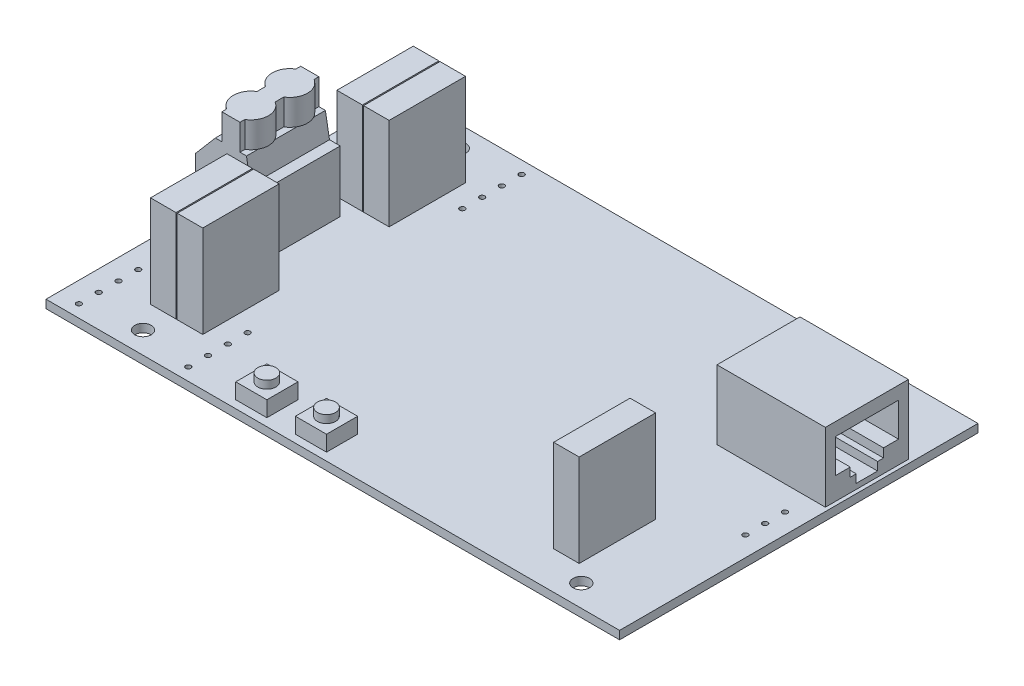
SolidWorks part; units mm, degrees
ref_plane "Front Plane" through (0, 0, 0) normal (0, 0, 1) x (1, 0, 0)
ref_plane "Top Plane" through (0, 0, 0) normal (0, 1, 0) x (1, 0, 0)
ref_plane "Right Plane" through (0, 0, 0) normal (1, 0, 0) x (0, 0, -1)
sketch "Sketch1" plane through (0, 0, 0) normal (0, 1, 0) x (1, 0, 0)
  line L0 (1.4606, 0) -> (0, 0) construction
  line L1 (-55.2894, -34.55) -> (55.2895, -34.55)
  line L2 (-55.2894, -34.55) -> (-55.2894, 34.55)
  line L3 (-55.2894, 34.55) -> (55.2895, 34.55)
  line L4 (55.2895, -34.55) -> (55.2895, 34.55)
  line L5 (-55.2894, -34.55) -> (55.2895, 34.55) construction
  line L6 (-55.2894, 34.55) -> (55.2895, -34.55) construction
  line L7 (-40.7894, -30.35) -> (43.7106, -30.35) construction
  line L8 (-40.7894, -30.35) -> (-40.7894, 30.35) construction
  line L9 (-40.7894, 30.35) -> (43.7106, 30.35) construction
  line L10 (43.7106, -30.35) -> (43.7106, 30.35) construction
  line L11 (-40.7894, -30.35) -> (43.7106, 30.35) construction
  line L12 (-40.7894, 30.35) -> (43.7106, -30.35) construction
  circle A0 centre (-40.7894, -30.35) radius 1.5875
  circle A1 centre (-40.7894, 30.35) radius 1.5875
  circle A2 centre (43.7106, 30.35) radius 1.5875
  circle A3 centre (43.7106, -30.35) radius 1.5875
  point P0 (0, 0)
  point P14 (0, 0)
  dimension "D3" = 3.175
  dimension "D6" = 4.2
  dimension "D7" = 14.5
  dimension "D1" = 69.1
  dimension "D2" = 110.5789
  dimension "D4" = 84.5
  dimension "D5" = 60.7
extrude "Boss-Extrude1" add sketch "Sketch1" against normal blind 1.5875
sketch "Sketch2" plane through (0, 0, 0) normal (0, 1, 0) x (1, 0, 0)
  line L0 (-30.2705, -20.705) -> (-30.2704, -24.515) construction
  line L1 (-30.2704, -24.515) -> (-30.2704, -28.325) construction
  line L2 (-30.2704, -28.325) -> (-30.2704, -32.135) construction
  line L3 (51.4795, 1.137) -> (51.4795, -6.483) construction
  line L4 (51.4795, 1.137) -> (51.4795, -2.673) construction
  line L5 (-30.2705, 24.505) -> (-30.2705, 20.695) construction
  line L6 (-30.2705, 32.125) -> (-30.2705, 28.315) construction
  line L7 (-30.2705, 28.315) -> (-30.2705, 24.505) construction
  line L8 (-51.2255, 28.315) -> (-51.2255, 24.505) construction
  line L9 (-51.3524, -24.515) -> (-51.3524, -28.325) construction
  line L10 (-51.2255, 24.505) -> (-51.2255, 20.695) construction
  line L11 (-51.3524, -28.325) -> (-51.3524, -32.135) construction
  line L12 (-51.2255, 32.125) -> (-51.2255, 28.315) construction
  line L13 (-51.3524, -20.705) -> (-51.3524, -24.515) construction
  line L15 (-55.2894, -34.55) -> (55.2895, -34.55) construction
  line L16 (-55.2894, 34.55) -> (-55.2894, -34.55) construction
  line L17 (55.2895, 34.55) -> (-55.2894, 34.55) construction
  line L18 (55.2895, -34.55) -> (55.2895, 34.55) construction
  circle A0 centre (51.4795, 1.137) radius 0.5
  circle A1 centre (51.4795, -2.673) radius 0.5
  circle A2 centre (51.4795, -6.483) radius 0.5
  circle A3 centre (-30.2705, -20.705) radius 0.5
  circle A4 centre (-30.2704, -24.515) radius 0.5
  circle A5 centre (-30.2704, -28.325) radius 0.5
  circle A6 centre (-30.2704, -32.135) radius 0.5
  circle A7 centre (-30.2705, 32.125) radius 0.5
  circle A8 centre (-30.2705, 20.695) radius 0.5
  circle A9 centre (-30.2705, 24.505) radius 0.5
  circle A10 centre (-30.2705, 28.315) radius 0.5
  circle A11 centre (-51.2255, 28.315) radius 0.5
  circle A12 centre (-51.2255, 24.505) radius 0.5
  circle A13 centre (-51.3524, -28.325) radius 0.5
  circle A14 centre (-51.3524, -20.705) radius 0.5
  circle A15 centre (-51.3524, -24.515) radius 0.5
  circle A16 centre (-51.2255, 32.125) radius 0.5
  circle A17 centre (-51.3524, -32.135) radius 0.5
  circle A18 centre (-51.2255, 20.695) radius 0.5
  dimension "D1" = 25.019
  dimension "D2" = 13.845
  dimension "D3" = 1
  dimension "D4" = 25.019
  dimension "D5" = 3.81
  dimension "D6" = 66.675
  dimension "D7" = 13.855
  dimension "D8" = 35.687
  dimension "D9" = 3.81
  dimension "D11" = 3.937
  dimension "D10" = 4.064
extrude "Cut-Extrude1" cut sketch "Sketch2" against normal through all
sketch "Sketch3" plane through (0, 0, 0) normal (0, 1, 0) x (1, 0, 0)
  line L0 (-34.2894, 10.598) -> (-34.2894, -10.598) construction
  line L1 (-44.3594, -10.598) -> (-39.4395, -10.598)
  line L2 (-44.3594, -10.598) -> (-44.3594, -25.33)
  line L3 (-44.3594, -25.33) -> (-39.4395, -25.33)
  line L4 (-39.4395, -10.598) -> (-39.4395, -25.33)
  line L5 (-44.3594, -10.598) -> (-39.4395, -25.33) construction
  line L6 (-44.3594, -25.33) -> (-39.4395, -10.598) construction
  line L11 (-39.2094, -25.33) -> (-34.2894, -25.33)
  line L12 (-39.2094, -25.33) -> (-39.2094, -10.598)
  line L13 (-39.2094, -10.598) -> (-34.2894, -10.598)
  line L14 (-34.2894, -25.33) -> (-34.2894, -10.598)
  line L15 (-39.2094, -25.33) -> (-34.2894, -10.598) construction
  line L16 (-39.2094, -10.598) -> (-34.2894, -25.33) construction
  line L17 (-39.2094, 10.598) -> (-34.2894, 10.598)
  line L18 (-39.2094, 10.598) -> (-39.2094, 25.33)
  line L19 (-39.2094, 25.33) -> (-34.2894, 25.33)
  line L20 (-34.2894, 10.598) -> (-34.2894, 25.33)
  line L21 (-39.2094, 10.598) -> (-34.2894, 25.33) construction
  line L22 (-39.2094, 25.33) -> (-34.2894, 10.598) construction
  line L23 (-44.3594, 10.598) -> (-39.4395, 10.598)
  line L24 (-44.3594, 10.598) -> (-44.3594, 25.33)
  line L25 (-44.3594, 25.33) -> (-39.4395, 25.33)
  line L26 (-39.4395, 10.598) -> (-39.4395, 25.33)
  line L27 (-44.3594, 10.598) -> (-39.4395, 25.33) construction
  line L28 (-44.3594, 25.33) -> (-39.4395, 10.598) construction
  line L29 (-34.2894, 0) -> (0, 0) construction
  line L30 (-55.2894, 34.55) -> (-55.2894, -34.55) construction
  line L31 (55.2895, -34.55) -> (55.2895, 34.55) construction
  line L32 (35.3095, -12.548) -> (40.2295, -12.548)
  line L33 (35.3095, -12.548) -> (35.3095, -27.28)
  line L34 (35.3095, -27.28) -> (40.2295, -27.28)
  line L35 (40.2295, -12.548) -> (40.2295, -27.28)
  line L36 (35.3095, -12.548) -> (40.2295, -27.28) construction
  line L37 (35.3095, -27.28) -> (40.2295, -12.548) construction
  line L38 (-55.2894, -34.55) -> (55.2895, -34.55) construction
  point P0 (-41.8994, -17.964)
  point P5 (-36.7494, -17.964)
  point P10 (-36.7494, 17.964)
  point P15 (-41.8994, 17.964)
  point P28 (37.7695, -19.914)
  dimension "D1" = 14.732
  dimension "D2" = 10.07
  dimension "D3" = 50.66
  dimension "D4" = 4.92
  dimension "D5" = 10.93
  dimension "D6" = 15.06
  dimension "D7" = 7.27
extrude "Boss-Extrude2" add sketch "Sketch3" along normal blind 17.78
sketch "Sketch4" plane through (0, 0, 0) normal (0, 1, 0) x (1, 0, 0)
  line L0 (-47.0694, 0) -> (0, 0) construction
  line L1 (-53.4194, -7.605) -> (-40.7194, -7.605)
  line L2 (-53.4194, -7.605) -> (-53.4194, 7.605)
  line L3 (-53.4194, 7.605) -> (-40.7194, 7.605)
  line L4 (-40.7194, -7.605) -> (-40.7194, 7.605)
  line L5 (-53.4194, -7.605) -> (-40.7194, 7.605) construction
  line L6 (-53.4194, 7.605) -> (-40.7194, -7.605) construction
  line L7 (-55.2894, 34.55) -> (-55.2894, -34.55) construction
  point P0 (-47.0694, 0)
  dimension "D1" = 15.21
  dimension "D2" = 12.7
  dimension "D3" = 1.87
extrude "Boss-Extrude3" add sketch "Sketch4" along normal blind 11.8
sketch "Sketch5" plane through (0, 0, 7.605) normal (0, 0, 1) x (1, 0, 0)
  line L0 (-53.4194, 11.8) -> (-40.7194, 11.8) construction
  line L1 (-53.4194, 11.8) -> (-42.7894, 11.8)
  line L2 (-53.4194, 11.8) -> (-49.5829, 16.3)
  line L3 (-49.5829, 16.3) -> (-43.5829, 16.3)
  line L4 (-43.5829, 16.3) -> (-42.7894, 11.8)
  line L5 (-53.4194, 0) -> (-40.7194, 0) construction
  line L6 (-40.7194, 11.8) -> (-40.7194, 0) construction
  dimension "D1" = 16.3
  dimension "D2" = 2.07
  dimension "D3" = 100
  dimension "D4" = 6
extrude "Boss-Extrude4" add sketch "Sketch5" against normal up to surface (15.21 mm away) up to face at (-47.0694, 5.9, -7.605)
sketch "Sketch6" plane through (0, 16.3, 0) normal (0, 1, 0) x (1, 0, 0)
  line L0 (-49.5829, 7.605) -> (-43.5829, 7.605) construction
  line L1 (-48.3329, 7.605) -> (-44.8329, 7.605)
  line L2 (-48.3329, 7.605) -> (-48.3329, 6.665)
  line L3 (-48.3329, -7.605) -> (-44.8329, -7.605)
  line L4 (-44.8329, 7.605) -> (-44.8329, 6.665)
  line L5 (-43.5829, -7.605) -> (-49.5829, -7.605) construction
  line L6 (-46.5829, 3.75) -> (-46.5829, -3.75) construction
  line L7 (-44.8329, 0) -> (-48.3329, 0) construction
  line L8 (-48.3329, -6.665) -> (-48.3329, -7.605)
  line L9 (-48.3329, 0.835) -> (-48.3329, -0.835)
  line L10 (-44.8329, 0.835) -> (-44.8329, -0.835)
  line L11 (-44.8329, -6.665) -> (-44.8329, -7.605)
  arc A0 (-48.3329, -0.835) -> (-48.3329, -6.665) centre (-46.5829, -3.75) ccw
  arc A1 (-44.8329, 0.835) -> (-44.8329, 6.665) centre (-46.5829, 3.75) ccw
  arc A2 (-48.3329, 6.665) -> (-48.3329, 0.835) centre (-46.5829, 3.75) ccw
  arc A3 (-44.8329, -6.665) -> (-44.8329, -0.835) centre (-46.5829, -3.75) ccw
  point P8 (-46.5829, -7.605)
  point P15 (-46.5829, 0)
  dimension "D2" = 6.8
  dimension "D3" = 7.5
  dimension "D1" = 3.5
extrude "Boss-Extrude5" add sketch "Sketch6" along normal blind 5
sketch "Sketch7" plane through (0, 0, 0) normal (0, 1, 0) x (1, 0, 0)
  line L0 (55.2895, 34.55) -> (-55.2894, 34.55) construction
  line L1 (33.6695, 5.85) -> (54.5695, 5.85)
  line L2 (33.6695, 5.85) -> (33.6695, 21.85)
  line L3 (33.6695, 21.85) -> (54.5695, 21.85)
  line L4 (54.5695, 5.85) -> (54.5695, 21.85)
  line L5 (55.2895, -34.55) -> (55.2895, 34.55) construction
  dimension "D1" = 12.7
  dimension "D2" = 0.72
  dimension "D3" = 16
  dimension "D4" = 20.9
extrude "Boss-Extrude6" add sketch "Sketch7" along normal blind 13.33
sketch "Sketch8" plane through (54.5695, 0, 0) normal (1, 0, 0) x (0, 0, -1)
  line L0 (15.91, 2.6125) -> (17.06, 2.6125)
  line L1 (7.75, 10.83) -> (19.95, 10.83)
  line L2 (7.75, 10.83) -> (7.75, 4.3125)
  line L3 (7.75, 4.3125) -> (10.64, 4.3125)
  line L4 (19.95, 10.83) -> (19.95, 4.3125)
  line L6 (10.64, 4.3125) -> (10.64, 2.6125)
  line L7 (10.64, 2.6125) -> (11.79, 2.6125)
  line L8 (17.06, 4.3125) -> (17.06, 2.6125)
  line L10 (11.79, 2.6125) -> (11.79, 1.0125)
  line L11 (11.79, 1.0125) -> (15.91, 1.0125)
  line L12 (15.91, 2.6125) -> (15.91, 1.0125)
  line L13 (17.06, 4.3125) -> (19.95, 4.3125)
  line L14 (13.85, 10.83) -> (13.85, 13.33) construction
  line L15 (5.85, 13.33) -> (21.85, 13.33) construction
  line L16 (5.85, 13.33) -> (5.85, 0) construction
  line L17 (-34.55, -1.5875) -> (34.55, -1.5875) construction
  dimension "D1" = 1.9
  dimension "D2" = 2.5
  dimension "D3" = 2.6
  dimension "D4" = 4.2
  dimension "D5" = 5.9
  dimension "D6" = 6.42
  dimension "D7" = 4.12
extrude "Cut-Extrude2" cut sketch "Sketch8" against normal blind 10.5
sketch "Sketch9" plane through (0, 0, 0) normal (0, 1, 0) x (1, 0, 0)
  line L0 (-55.2894, -34.55) -> (55.2895, -34.55) construction
  line L1 (-20.2105, -27.05) -> (-14.2105, -27.05)
  line L2 (-20.2105, -27.05) -> (-20.2105, -33.05)
  line L3 (-20.2105, -33.05) -> (-14.2105, -33.05)
  line L4 (-14.2105, -27.05) -> (-14.2105, -33.05)
  line L5 (-8.7105, -27.05) -> (-2.7105, -27.05)
  line L6 (-8.7105, -27.05) -> (-8.7105, -33.05)
  line L7 (-8.7105, -33.05) -> (-2.7105, -33.05)
  line L8 (-2.7105, -27.05) -> (-2.7105, -33.05)
  line L9 (55.2895, -34.55) -> (55.2895, 34.55) construction
  dimension "D1" = 6
  dimension "D2" = 1.5
  dimension "D3" = 17.5
  dimension "D4" = 58
extrude "Boss-Extrude7" add sketch "Sketch9" along normal blind 3
sketch "Sketch10" plane through (0, 3, 0) normal (0, 1, 0) x (1, 0, 0)
  line L0 (-14.2105, -27.05) -> (-20.2105, -33.05) construction
  line L1 (-2.7105, -27.05) -> (-8.7105, -33.05) construction
  circle A0 centre (-17.2105, -30.05) radius 1.75
  circle A1 centre (-5.7105, -30.05) radius 1.75
  dimension "D1" = 3.5
extrude "Boss-Extrude8" add sketch "Sketch10" along normal blind 1.5
